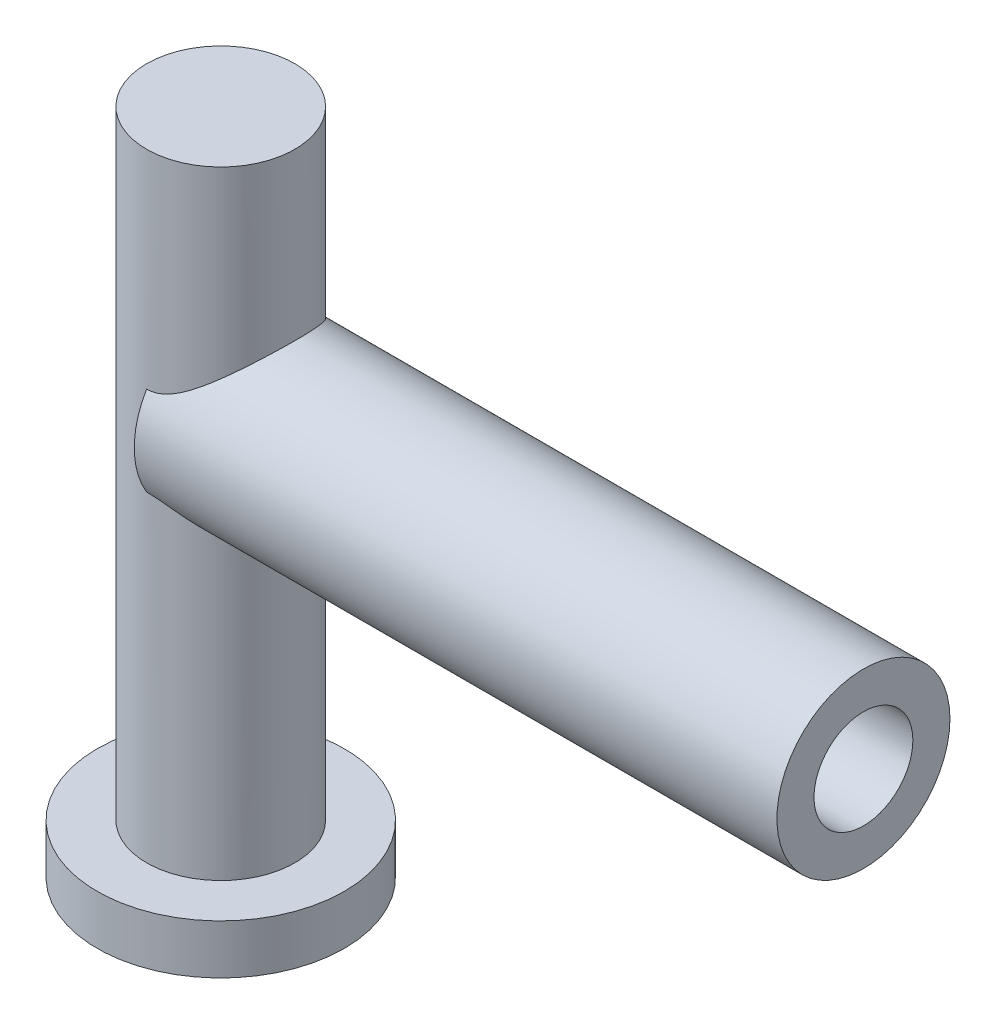
SolidWorks part; units mm, degrees
ref_plane "Front Plane" through (0, 0, 0) normal (0, 0, 1) x (1, 0, 0)
ref_plane "Top Plane" through (0, 0, 0) normal (0, 1, 0) x (1, 0, 0)
ref_plane "Right Plane" through (0, 0, 0) normal (1, 0, 0) x (0, 0, -1)
sketch "Sketch1" plane through (0, 0, 0) normal (0, 0, 1) x (1, 0, 0)
  line L0 (0, 135) -> (0, -135)
  line L1 (0, -135) -> (50, -135)
  line L2 (50, -135) -> (50, -115)
  line L3 (50, -115) -> (30, -115)
  line L4 (30, -115) -> (30, 135)
  line L5 (30, 135) -> (0, 135)
  point P4 (0, 0)
  dimension "D1" = 270
  dimension "D2" = 50
  dimension "D3" = 30
  dimension "D4" = 20
revolve "Revolve1" add sketch "Sketch1" angle 360 about L0
ref_axis "Axis1" through (0, 0, -55) along (0, 0, 1)
ref_plane "Plane1" through (0, 0, 0) normal (1, 0, 0) x (0, 0, 1)
sketch "Sketch2" plane through (0, 0, 0) normal (1, 0, 0) x (0, 0, 1)
  circle A0 centre (0, -32.949) radius 35
  ellipse E0 centre (0, -132.949) end of major axis (-30, -132.949) minor radius 5.2094 construction
  dimension "D1" = 70
  dimension "D2" = 100
extrude "Boss-Extrude1" add sketch "Sketch2" along normal blind 260
sketch "Sketch3" plane through (260, 0, 0) normal (1, 0, 0) x (0, 0, -1)
  circle A0 centre (0, 32.949) radius 20
  dimension "D1" = 40
extrude "Cut-Extrude1" cut sketch "Sketch3" against normal through all
